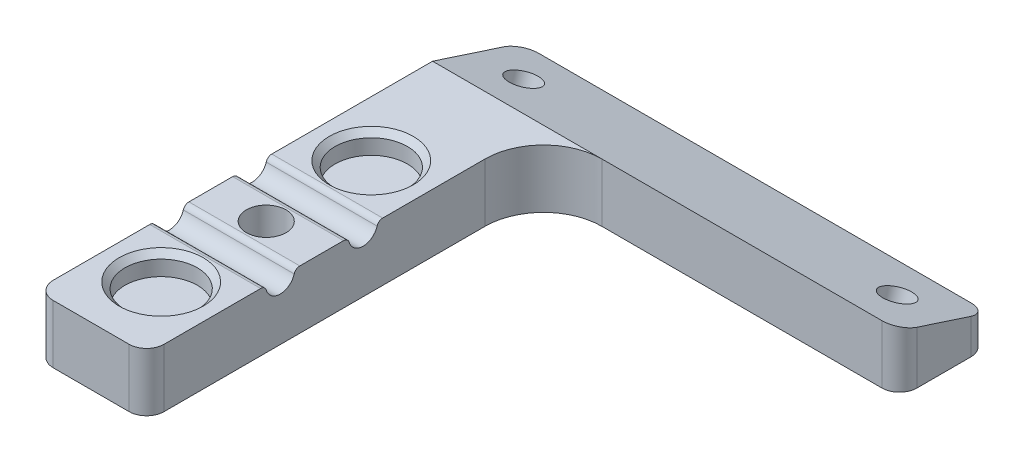
SolidWorks part; units mm, degrees
ref_plane "Front Plane" through (0, 0, 0) normal (0, 0, 1) x (1, 0, 0)
ref_plane "Top Plane" through (0, 0, 0) normal (0, 1, 0) x (1, 0, 0)
ref_plane "Right Plane" through (0, 0, 0) normal (1, 0, 0) x (0, 0, -1)
sketch "Sketch1" plane through (0, 0, 0) normal (0, 1, 0) x (1, 0, 0)
  line L1 (-4.75, -15) -> (4.75, -15)
  line L2 (-4.75, -15) -> (-4.75, 15)
  line L3 (-4.75, 15) -> (4.75, 15)
  line L4 (4.75, -15) -> (4.75, 15)
  line L5 (-4.75, -15) -> (4.75, 15) construction
  line L6 (-4.75, 15) -> (4.75, -15) construction
  point P0 (0, 0)
  dimension "D1" = 9.5
  dimension "D2" = 30
extrude "Boss-Extrude1" add sketch "Sketch1" along normal blind 5
sketch "Sketch2" plane through (0, 5, 0) normal (0, 1, 0) x (1, 0, 0)
  line L0 (0, 9) -> (0, -9) construction
  line L1 (4.75, 15) -> (-4.75, 15) construction
  circle A0 centre (0, 9) radius 3.1
  circle A1 centre (0, 0) radius 1.7
  circle A2 centre (0, -9) radius 3.1
  dimension "D1" = 6.2
  dimension "D2" = 3.4
  dimension "D3" = 6
extrude "Cut-Extrude1" cut sketch "Sketch2" against normal through all
sketch "Sketch8" plane through (0, 0, 0) normal (0, -1, 0) x (1, 0, 0)
  circle A0 centre (0, 9) radius 3.1
  circle A1 centre (0, -9) radius 3.1
  circle A2 centre (0, -9) radius 3.1 construction
  circle A3 centre (0, 9) radius 3.1 construction
extrude "Boss-Extrude3" add sketch "Sketch8" against normal offset from surface (3.2 mm away) 1.8 up to face at (0, 5, 12.1)
chamfer "Chamfer1" distance 0.5 angle 45 2 edges at (0, 5, 12.1) (0, 5, -5.9)
sketch "Sketch3" plane through (0, 5, 0) normal (0, 1, 0) x (1, 0, 0)
  line L0 (-4.75, 15) -> (-4.75, 19)
  line L1 (-4.75, 29) -> (35.25, 29)
  line L2 (-4.75, 29) -> (-4.75, 19)
  line L3 (4.75, 19) -> (35.25, 19)
  line L4 (35.25, 29) -> (35.25, 19)
  line L5 (-4.75, 29) -> (35.25, 19) construction
  line L6 (-4.75, 19) -> (35.25, 29) construction
  line L7 (4.75, 15) -> (4.75, 19)
  line L8 (4.75, -15) -> (4.75, 15) construction
  line L9 (-4.75, 15) -> (-4.75, -15) construction
  line L10 (4.75, 15) -> (-4.75, 15)
  point P0 (15.25, 24)
  dimension "D1" = 40
  dimension "D2" = 4
  dimension "D3" = 10
extrude "Boss-Extrude2" add sketch "Sketch3" against normal up to surface (5 mm away) up to face at (0, 0, 1.7)
sketch "Sketch5" plane through (35.25, 0, 0) normal (1, 0, 0) x (0, 0, -1)
  line L0 (19, 5) -> (29, 1.7508)
  line L1 (29, 0) -> (29, 5) construction
  line L2 (29, 1.7508) -> (29, 5)
  line L3 (29, 5) -> (19, 5)
  dimension "D1" = 18
extrude "Cut-Extrude2" cut sketch "Sketch5" against normal through all
sketch "Sketch6" plane through (0, 10.1065, -3.2838) normal (0, 0.9511, -0.309) x (1, 0, 0)
  line L0 (31.25, 20.525) -> (-0.75, 20.525) construction
  line L1 (-0.75, 20.525) -> (-4.75, 20.525) construction
  line L2 (-4.75, 16.525) -> (-4.75, 27.0396) construction
  line L3 (31.25, 20.525) -> (35.25, 20.525) construction
  line L5 (35.25, 16.525) -> (35.25, 27.0396) construction
  line L6 (-4.75, 16.525) -> (4.75, 16.525) construction
  circle A0 centre (-0.75, 20.525) radius 1.3
  circle A1 centre (31.25, 20.525) radius 1.3
  dimension "D1" = 2.6
  dimension "D2" = 32
  dimension "D3" = 4
extrude "Cut-Extrude3" cut sketch "Sketch6" against normal through all
sketch "Sketch9" plane through (35.25, 0, 0) normal (1, 0, 0) x (0, 0, -1)
  line L1 (29, 0) -> (26.6085, 0)
  line L2 (29, 0) -> (29, 2.5279)
  line L3 (29, 2.5279) -> (26.6085, 2.5279)
  line L4 (26.6085, 0) -> (26.6085, 2.5279)
  line L5 (29, 0) -> (26.6085, 2.5279) construction
  line L6 (29, 2.5279) -> (26.6085, 0) construction
  line L7 (19, 5) -> (29, 1.7508) construction
  point P0 (27.8042, 1.2639)
  dimension "D1" = 2.7
extrude "Cut-Extrude4" cut sketch "Sketch9" against normal through all
fillet "Fillet2" radius 1.5 5 edges at (35.25, 2.5, -19) (-4.75, 2.5, 15) (4.75, 2.5, 15) (-4.75, 1.2639, -26.6085) (35.25, 1.2639, -26.6085)
fillet "Fillet1" radius 5 1 edges at (4.75, 2.5, -19)
sketch "Sketch10" plane through (0, 0, 0) normal (0, -1, 0) x (1, 0, 0)
  circle A0 centre (0, 0) radius 3.25
  dimension "D1" = 6.5
extrude "Cut-Extrude5" cut sketch "Sketch10" against normal blind 2
sketch "Sketch13" plane through (-4.75, 0, 0) normal (-1, 0, 0) x (0, 0, 1)
  line L0 (-19, 5) -> (13.5, 5) construction
  line L2 (0, -2.75) -> (0, 2.75) construction
  line L3 (-3.55, 5) -> (3.55, 5) construction
  circle A0 centre (-3.55, 5) radius 1.25
  circle A1 centre (3.55, 5) radius 1.25
  point P8 (0, 5)
  dimension "D2" = 2.5
  dimension "D1" = 3.55
extrude "Cut-Extrude6" cut sketch "Sketch13" against normal through all
fillet "Fillet3" radius 0.5 4 edges at (0, 5, 4.8) (0, 5, 2.3) (0, 5, -2.3) (0, 5, -4.8)
equation "\"M3_d\"= 3.4"
equation "\"M3_tap_d\"=2.6"
equation "\"D2@Sketch2\"=\"M3_d\""
equation "\"D1@Sketch6\"=\"M3_tap_d\""
